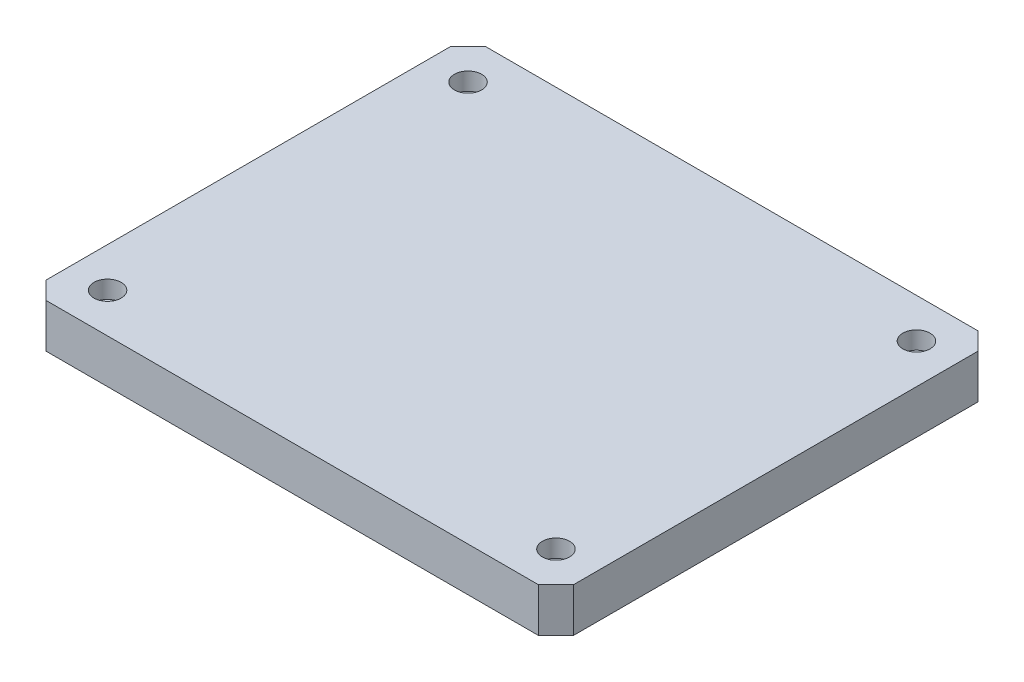
SolidWorks part; units mm, degrees
ref_plane "Front Plane" through (0, 0, 0) normal (0, 0, 1) x (1, 0, 0)
ref_plane "Top Plane" through (0, 0, 0) normal (0, 1, 0) x (1, 0, 0)
ref_plane "Right Plane" through (0, 0, 0) normal (1, 0, 0) x (0, 0, -1)
sketch "Sketch1" plane through (0, 0, 0) normal (0, 1, 0) x (1, 0, 0)
  line L1 (0, 0) -> (60, 0)
  line L2 (0, 0) -> (0, 50)
  line L3 (0, 50) -> (60, 50)
  line L4 (60, 0) -> (60, 50)
  dimension "D1" = 50
  dimension "D2" = 60
extrude "Boss-Extrude1" add sketch "Sketch1" along normal blind 5
chamfer "Chamfer1" distance 2 angle 45 4 edges at (60, 2.5, 0) (60, 2.5, -50) (0, 2.5, 0) (0, 2.5, -50)
sketch "Sketch2" plane through (0, 5, 0) normal (0, 1, 0) x (1, 0, 0)
  circle A1 centre (55.5, 4.5) radius 1.55
  circle A2 centre (55.5, 4.5) radius 1.55
  circle A3 centre (4.5, 4.5) radius 1.55
  circle A4 centre (4.5, 4.5) radius 1.55
  circle A5 centre (4.5, 45.5) radius 1.55
  circle A6 centre (4.5, 45.5) radius 1.55
  circle A7 centre (55.5, 45.5) radius 1.55
  circle A8 centre (55.5, 45.5) radius 1.55
  dimension "D1" = 0
  dimension "D2" = 0
  dimension "D3" = 0
  dimension "D4" = 0
extrude "Cut-Extrude1" cut sketch "Sketch2" against normal blind 2
